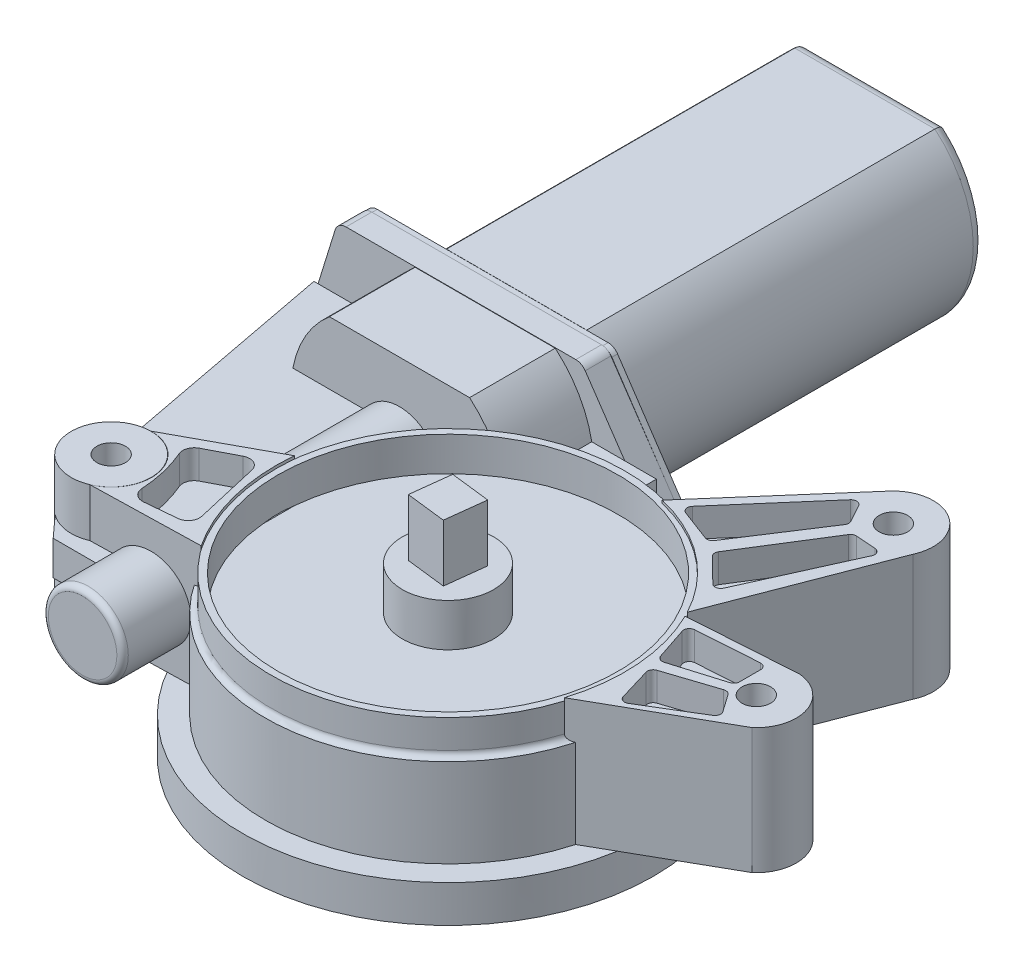
SolidWorks part; units mm, degrees
ref_plane "Спереди" through (0, 0, 0) normal (0, 0, 1) x (1, 0, 0)
ref_plane "Сверху" through (0, 0, 0) normal (0, 1, 0) x (1, 0, 0)
ref_plane "Справа" through (0, 0, 0) normal (1, 0, 0) x (0, 0, -1)
sketch "Эскиз3" plane through (0, 0, 0) normal (0, 0, 1) x (1, 0, 0)
  line L0 (0, 0) -> (56.6194, 0) construction
  line L1 (-12.278, 14.5) -> (12.278, 14.5)
  line L2 (-12.278, -14.5) -> (12.278, -14.5)
  arc A0 (-12.278, 14.5) -> (-12.278, -14.5) centre (0, 0) ccw
  arc A1 (12.278, -14.5) -> (12.278, 14.5) centre (0, 0) ccw
  dimension "D1" = 14.5
extrude "Вытянуть1" add sketch "Эскиз3" along normal blind 63
sketch "Эскиз4" plane through (0, 0, 0) normal (0, 0, -1) x (-1, 0, 0)
  circle A0 centre (0, 0) radius 6.75
extrude "Вытянуть2" add sketch "Эскиз4" along normal blind 5
sketch "Эскиз5" plane through (0, 0, -5) normal (0, 0, -1) x (-1, 0, 0)
  circle A0 centre (0, 0) radius 2.5
extrude "Вытянуть3" add sketch "Эскиз5" along normal blind 2 draft 33
sketch "Эскиз7" plane through (0, 0, 63) normal (0, 0, 1) x (1, 0, 0)
  line L0 (-29.9997, 1.118) -> (-26.3061, 13.0633)
  line L1 (-24.3954, -14.4725) -> (27.9997, -14.4725)
  line L2 (-29.9997, -1.118) -> (-29.9997, 1.118)
  line L3 (-24.3954, 14.4725) -> (16.0407, 14.4725)
  line L4 (29.9997, -12.4725) -> (29.9997, -5.3043)
  line L5 (-26.4064, -12.739) -> (20.265, 9.7763) construction
  line L6 (-26.4064, 12.739) -> (29.9997, -14.4725) construction
  line L7 (-29.9997, 0) -> (-36.554, 0) construction
  line L8 (-29.9997, -1.118) -> (-26.3061, -13.0633)
  line L9 (17.7001, 13.5889) -> (29.6591, -4.1879)
  arc A0 (-24.3954, 14.4725) -> (-26.3061, 13.0633) centre (-24.3954, 12.4725) ccw
  arc A1 (-24.3954, -14.4725) -> (-26.3061, -13.0633) centre (-24.3954, -12.4725) cw
  arc A2 (17.7001, 13.5889) -> (16.0407, 14.4725) centre (16.0407, 12.4725) ccw
  arc A3 (29.6591, -4.1879) -> (29.9997, -5.3043) centre (27.9997, -5.3043) cw
  arc A4 (27.9997, -14.4725) -> (29.9997, -12.4725) centre (27.9997, -12.4725) ccw
  point P0 (0, 0)
  point P14 (-25.8704, 14.4725)
  point P17 (-25.8704, -14.4725)
  dimension "D1" = 2
  dimension "D2" = 2
extrude "Вытянуть4" add sketch "Эскиз7" along normal blind 1
ref_plane "Плоскость1" through (0, -16.5, 0) normal (0, -1, 0) x (1, 0, 0)
sketch "Эскиз8" plane through (0, -16.5, 0) normal (0, -1, 0) x (1, 0, 0)
  line L0 (0, 0) -> (0, 81.1276) construction
  line L1 (23.2237, 64) -> (84.0137, 64) construction
  circle A0 centre (34, 109) radius 36
  dimension "D1" = 45
  dimension "D2" = 34
extrude "Вытянуть5" add sketch "Эскиз8" against normal blind 6.5 separate body
sketch "Эскиз10" plane through (0, -10, 0) normal (0, -1, 0) x (-1, 0, 0)
  circle A0 centre (-34, -109) radius 32
extrude "Вытянуть6" add sketch "Эскиз10" against normal blind 15.5
sketch "Эскиз11" plane through (0, 5.5, 0) normal (0, 1, 0) x (1, 0, 0)
  circle A0 centre (34, -109) radius 31
  circle A1 centre (34, -109) radius 29.8
extrude "Вытянуть7" add sketch "Эскиз11" along normal blind 6
fillet "Скругление1" radius 1 1 edges at (34, 5.5, 78)
sketch "Эскиз12" plane through (0, -16.5, 0) normal (0, 1, 0) x (-1, 0, 0)
  line L0 (-34, 145) -> (-34, 159.637) construction
  line L1 (-70, 109) -> (-97.217, 109) construction
  line L2 (-44.5372, 139.4635) -> (-23.4628, 139.4635)
  line L3 (-21.7278, 136.4684) -> (-32.2651, 118.0963)
  line L4 (-46.2722, 136.4684) -> (-35.7349, 118.0963)
  line L5 (-16.3477, 133.3622) -> (-26.9898, 115.0506)
  line L6 (-4.0756, 112.1062) -> (-25.2549, 112.0457)
  line L7 (-12.8865, 133.3573) -> (-2.3492, 115.1062)
  line L8 (-4.0756, 105.8938) -> (-25.2549, 105.9543)
  line L9 (-16.3477, 84.6378) -> (-26.9898, 102.9494)
  line L10 (-2.3492, 102.8938) -> (-12.8865, 84.6427)
  line L11 (-21.7278, 81.5316) -> (-32.2651, 99.9037)
  line L12 (-46.2722, 81.5316) -> (-35.7349, 99.9037)
  line L13 (-23.4628, 78.5365) -> (-44.5372, 78.5365)
  line L14 (-51.6523, 84.6378) -> (-41.0102, 102.9494)
  line L15 (-63.9244, 105.8938) -> (-42.7451, 105.9543)
  line L16 (-55.1135, 84.6427) -> (-65.6508, 102.8938)
  line L17 (-63.9244, 112.1062) -> (-42.7451, 112.0457)
  line L18 (-51.6523, 133.3622) -> (-41.0102, 115.0506)
  line L19 (-65.6508, 115.1062) -> (-55.1135, 133.3573)
  arc A0 (-23.4628, 139.4635) -> (-21.7278, 136.4684) centre (-23.4628, 137.4635) cw
  arc A1 (-46.2722, 136.4684) -> (-44.5372, 139.4635) centre (-44.5372, 137.4635) cw
  arc A2 (-32.2651, 118.0963) -> (-35.7349, 118.0963) centre (-34, 119.0914) cw
  arc A3 (-25.2549, 112.0457) -> (-26.9898, 115.0506) centre (-25.2606, 114.0457) cw
  arc A4 (-2.3492, 115.1062) -> (-4.0756, 112.1062) centre (-4.0813, 114.1062) cw
  arc A5 (-16.3477, 133.3622) -> (-12.8865, 133.3573) centre (-14.6185, 132.3573) cw
  arc A6 (-26.9898, 102.9494) -> (-25.2549, 105.9543) centre (-25.2606, 103.9543) cw
  arc A7 (-12.8865, 84.6427) -> (-16.3477, 84.6378) centre (-14.6185, 85.6427) cw
  arc A8 (-4.0756, 105.8938) -> (-2.3492, 102.8938) centre (-4.0813, 103.8938) cw
  arc A9 (-35.7349, 99.9037) -> (-32.2651, 99.9037) centre (-34, 98.9086) cw
  arc A10 (-44.5372, 78.5365) -> (-46.2722, 81.5316) centre (-44.5372, 80.5365) cw
  arc A11 (-21.7278, 81.5316) -> (-23.4628, 78.5365) centre (-23.4628, 80.5365) cw
  arc A12 (-42.7451, 105.9543) -> (-41.0102, 102.9494) centre (-42.7394, 103.9543) cw
  arc A13 (-65.6508, 102.8938) -> (-63.9244, 105.8938) centre (-63.9187, 103.8938) cw
  arc A14 (-51.6523, 84.6378) -> (-55.1135, 84.6427) centre (-53.3815, 85.6427) cw
  arc A15 (-41.0102, 115.0506) -> (-42.7451, 112.0457) centre (-42.7394, 114.0457) cw
  arc A16 (-55.1135, 133.3573) -> (-51.6523, 133.3622) centre (-53.3815, 132.3573) cw
  arc A17 (-63.9244, 112.1062) -> (-65.6508, 115.1062) centre (-63.9187, 114.1062) cw
  point P9 (-20.0101, 139.4635)
  point P12 (-47.9899, 139.4635)
  point P15 (-34, 115.0714)
  dimension "D1" = 2
extrude "Вытянуть8" cut sketch "Эскиз12" along normal blind 1.2
sketch "Эскиз13" plane through (0, 5.5, 0) normal (0, 1, 0) x (1, 0, 0)
  circle A0 centre (34, -109) radius 8
extrude "Вытянуть9" add sketch "Эскиз13" along normal blind 7.5
sketch "Эскиз14" plane through (0, 13, 0) normal (0, 1, 0) x (1, 0, 0)
  line L1 (30.9351, -105.1133) -> (30.1133, -112.0649)
  line L2 (30.1133, -112.0649) -> (37.0649, -112.8867)
  line L3 (37.0649, -112.8867) -> (37.8867, -105.9351)
  line L4 (37.8867, -105.9351) -> (30.9351, -105.1133)
  circle A0 centre (34, -109) radius 3.5 construction
extrude "Вытянуть10" add sketch "Эскиз14" along normal blind 10
sketch "Эскиз15" plane through (0, 0, 64) normal (0, 0, 1) x (1, 0, 0)
  circle A0 centre (0, 0) radius 7
extrude "Вытянуть11" add sketch "Эскиз15" along normal blind 75
sketch "Эскиз16" plane through (0, 0, 64) normal (0, 0, 1) x (1, 0, 0)
  line L0 (12.278, 14.5) -> (-12.278, 14.5)
  line L1 (12.278, 14.5) -> (-12.278, 14.5) construction
  line L2 (12.278, -14.5) -> (-12.278, -14.5)
  arc A0 (-12.278, 14.5) -> (-12.278, -14.5) centre (0, 0) ccw
  arc A1 (12.278, -14.5) -> (12.278, 14.5) centre (0, 0) ccw
extrude "Вытянуть12" add sketch "Эскиз16" along normal blind 19.5
sketch "Эскиз17" plane through (0, 0, 64) normal (0, 0, 1) x (1, 0, 0)
  line L0 (-26.2716, 13.1654) -> (-29.9899, 1.1498)
  line L1 (15.8793, 14.5741) -> (-24.361, 14.5741)
  line L2 (30.0005, -5.2705) -> (30.0005, -12.4733)
  line L3 (28.0005, -14.4733) -> (-24.3951, -14.4733)
  line L4 (-29.9899, 1.1498) -> (-29.9899, -1.1315)
  line L7 (-29.9899, -1.1315) -> (-26.3061, -13.0633)
  line L8 (-26.3061, 13.0633) -> (-29.9997, 1.118) construction
  line L9 (29.6549, -4.1467) -> (17.5338, 13.6979)
  arc A0 (-26.2716, 13.1654) -> (-24.361, 14.5741) centre (-24.361, 12.5741) cw
  arc A1 (-26.3061, -13.0633) -> (-24.3951, -14.4733) centre (-24.3951, -12.4733) ccw
  arc A2 (-24.3954, 14.4725) -> (-26.3061, 13.0633) centre (-24.3954, 12.4725) ccw construction
  arc A3 (15.8793, 14.5741) -> (17.5338, 13.6979) centre (15.8793, 12.5741) cw
  arc A4 (28.0005, -14.4733) -> (30.0005, -12.4733) centre (28.0005, -12.4733) ccw
  arc A5 (29.6549, -4.1467) -> (30.0005, -5.2705) centre (28.0005, -5.2705) cw
  dimension "D1" = 2
  dimension "D2" = 2
  dimension "D3" = 2
  dimension "D4" = 2
extrude "Вытянуть13" add sketch "Эскиз17" along normal blind 4.5
fillet "Скругление2" radius 1 1 edges at (7, 0, 139)
ref_plane "Плоскость2" through (0, -2.5, 0) normal (0, -1, 0) x (1, 0, 0)
ref_plane "Плоскость3" through (0, -10, 0) normal (0, 1, 0) x (-1, 0, 0)
sketch "Эскиз19" plane through (0, -10, 0) normal (0, 1, 0) x (-1, 0, 0)
  line L1 (-16.0407, 64) -> (24.3954, 64) construction
  line L2 (0, 0) -> (0, -45.8668) construction
  circle A0 centre (13, 121) radius 7
  circle A1 centre (13, 121) radius 2.5
  dimension "D1" = 57
  dimension "D2" = 13
extrude "Вытянуть16" add sketch "Эскиз19" along normal blind 22
sketch "Эскиз18" plane through (0, -2.5, 0) normal (0, -1, 0) x (1, 0, 0)
  line L0 (-29.9899, 68.5) -> (-20, 121)
  line L1 (-13.853, 130.3043) -> (2.1987, 130.3043)
  line L2 (-17.229, 126.5781) -> (-13.853, 130.3043)
  line L3 (30.0005, 77.2509) -> (30.0005, 68.5)
  line L4 (-29.9899, 68.5) -> (30.0005, 68.5)
  line L5 (2.1987, 112.5605) -> (2.1987, 130.3043)
  circle A0 centre (-13, 121) radius 7 construction
  arc A1 (30.0005, 77.2509) -> (2.1987, 112.5605) centre (34, 109) cw
  arc A2 (18.1865, 81.1803) -> (4.3301, 120.9874) centre (34, 109) ccw construction
  arc A4 (-20, 121) -> (-17.229, 126.5781) centre (-13, 121) ccw
extrude "Вытянуть15" add sketch "Эскиз18" against normal blind 6
sketch "Эскиз20" plane through (0, -10, 0) normal (0, 1, 0) x (-1, 0, 0)
  line L0 (13.0336, 113.982) -> (-3.2391, 105.157)
  line L1 (10.2818, 127.4507) -> (-8.7473, 126.9805)
  arc A0 (17.229, 126.5781) -> (6.0622, 121.9309) centre (13, 121) ccw construction
  circle A1 centre (13, 121) radius 7 construction
  arc A6 (-3.2391, 105.157) -> (-8.7473, 126.9805) centre (-37.2063, 108.1908) ccw
  arc A7 (13.0336, 113.982) -> (10.2818, 127.4507) centre (12.9558, 120.9816) cw
  arc A8 (-16.3719, 83.5) -> (-17.8536, 82.537) centre (-34, 109) ccw construction
extrude "Вытянуть21" add sketch "Эскиз20" along normal blind 22 separate body
sketch "Эскиз21" plane through (0, 12, 0) normal (0, 1, 0) x (1, 0, 0)
  line L0 (-6.2428, -112.3443) -> (-1.1739, -109.7169)
  line L1 (1.6954, -111.0431) -> (4.3195, -122.4246)
  line L2 (2.554, -124.8655) -> (-2.9539, -125.3725)
  arc A0 (-7.1603, -114.9089) -> (-5.1338, -123.4968) centre (-30.6107, -124.9754) cw
  arc A1 (-6.2428, -112.3443) -> (-7.1603, -114.9089) centre (-5.3224, -114.12) ccw
  arc A2 (1.6954, -111.0431) -> (-1.1739, -109.7169) centre (-0.2535, -111.4925) ccw
  arc A3 (2.554, -124.8655) -> (4.3195, -122.4246) centre (2.3706, -122.874) ccw
  arc A4 (-5.1338, -123.4968) -> (-2.9539, -125.3725) centre (-3.1372, -123.381) ccw
  dimension "D1" = 2
extrude "Вытянуть23" cut sketch "Эскиз21" against normal blind 5
sketch "Эскиз22" plane through (0, -10, 0) normal (0, -1, 0) x (1, 0, 0)
  line L0 (-2.6512, 125.3994) -> (3.0523, 125.1404)
  line L1 (4.874, 122.5572) -> (1.4559, 111.3884)
  line L2 (-1.2936, 110.1573) -> (-6.317, 112.4722)
  arc A0 (-4.728, 123.6372) -> (-7.267, 115.1865) centre (-30.0699, 126.6445) cw
  arc A1 (-2.6512, 125.3994) -> (-4.728, 123.6372) centre (-2.742, 123.4015) ccw
  arc A2 (4.874, 122.5572) -> (3.0523, 125.1404) centre (2.9616, 123.1425) ccw
  arc A3 (-1.2936, 110.1573) -> (1.4559, 111.3884) centre (-0.4566, 111.9737) ccw
  arc A4 (-7.267, 115.1865) -> (-6.317, 112.4722) centre (-5.48, 114.2886) ccw
extrude "Вытянуть24" cut sketch "Эскиз22" against normal blind 5
sketch "Эскиз23" plane through (0, -10, 0) normal (0, 1, 0) x (-1, 0, 0)
  line L0 (0, 0) -> (0, -17.6371) construction
  line L1 (-27.9997, 63) -> (-142.4972, 63) construction
  line L2 (-60.6873, 58.442) -> (-42.1989, 79.6831)
  line L3 (-72.3707, 65.9008) -> (-61.3848, 94.4717)
  arc A0 (-72.3707, 65.9008) -> (-60.6873, 58.442) centre (-66, 63) ccw
  circle A1 centre (-66, 63) radius 2.5
  circle A2 centre (-34, 109) radius 31 construction
  arc A5 (-42.1989, 79.6831) -> (-61.3848, 94.4717) centre (-35.4039, 108.3383) cw
  dimension "D1" = 66
extrude "Вытянуть27" add sketch "Эскиз23" along normal up to surface (22 mm away) separate body up to face at (-1.718, 12, 118.0081)
sketch "Эскиз24" plane through (0, 12, 0) normal (0, 1, 0) x (1, 0, 0)
  line L0 (66, -63) -> (69.7667, -57.0998) construction
  line L1 (45.7799, -77.9636) -> (58.6063, -63.1419)
  line L2 (60.2372, -63.3116) -> (61.9309, -66.3685)
  line L3 (61.8946, -67.3981) -> (52.8928, -81.2471)
  line L4 (51.701, -81.6376) -> (46.1827, -79.5534)
  line L5 (55.112, -83.8152) -> (59.3252, -87.9437)
  line L6 (63.7383, -68.5752) -> (54.9646, -82.5698)
  line L7 (68.1428, -68.3587) -> (64.6571, -68.1089)
  line L8 (60.9369, -87.6399) -> (68.9832, -69.7666)
  arc A1 (60.2372, -63.3116) -> (58.6063, -63.1419) centre (59.3625, -63.7963) ccw
  arc A2 (61.8946, -67.3981) -> (61.9309, -66.3685) centre (61.0562, -66.8531) ccw
  arc A3 (51.701, -81.6376) -> (52.8928, -81.2471) centre (52.0543, -80.7021) ccw
  arc A4 (45.7799, -77.9636) -> (46.1827, -79.5534) centre (46.5361, -78.6179) ccw
  arc A5 (60.9369, -87.6399) -> (59.3252, -87.9437) centre (60.0251, -87.2294) cw
  arc A6 (55.112, -83.8152) -> (54.9646, -82.5698) centre (55.8119, -83.1009) cw
  arc A7 (63.7383, -68.5752) -> (64.6571, -68.1089) centre (64.5856, -69.1064) cw
  arc A8 (68.1428, -68.3587) -> (68.9832, -69.7666) centre (68.0714, -69.3561) cw
  dimension "D1" = 1
extrude "Вытянуть28" cut sketch "Эскиз24" against normal blind 5
sketch "Эскиз25" plane through (0, -10, 0) normal (0, -1, 0) x (1, 0, 0)
  line L0 (46.1827, 79.5534) -> (51.701, 81.6376)
  line L1 (52.8928, 81.2471) -> (61.8946, 67.3981)
  line L2 (61.9309, 66.3685) -> (60.2372, 63.3116)
  line L3 (58.6063, 63.1419) -> (45.7799, 77.9636)
  line L4 (66, 63) -> (69.7667, 57.0998) construction
  line L5 (59.3252, 87.9437) -> (55.112, 83.8152)
  line L6 (54.9646, 82.5698) -> (63.7383, 68.5752)
  line L7 (64.6571, 68.1089) -> (68.1428, 68.3587)
  line L8 (68.9832, 69.7666) -> (60.9369, 87.6399)
  arc A0 (55.112, 83.8152) -> (54.9646, 82.5698) centre (55.8119, 83.1009) ccw
  arc A1 (60.2372, 63.3116) -> (58.6063, 63.1419) centre (59.3625, 63.7963) cw
  arc A2 (61.9309, 66.3685) -> (61.8946, 67.3981) centre (61.0562, 66.8531) ccw
  arc A3 (51.701, 81.6376) -> (52.8928, 81.2471) centre (52.0543, 80.7021) cw
  arc A4 (45.7799, 77.9636) -> (46.1827, 79.5534) centre (46.5361, 78.6179) cw
  arc A5 (64.6571, 68.1089) -> (63.7383, 68.5752) centre (64.5856, 69.1064) cw
  arc A6 (68.1428, 68.3587) -> (68.9832, 69.7666) centre (68.0714, 69.3561) ccw
  arc A7 (60.9369, 87.6399) -> (59.3252, 87.9437) centre (60.0251, 87.2294) ccw
  dimension "D1" = 1
extrude "Вытянуть29" cut sketch "Эскиз25" against normal blind 5
sketch "Эскиз26" plane through (0, -10, 0) normal (0, 1, 0) x (-1, 0, 0)
  line L0 (-27.2099, 64) -> (-121.7072, 64) construction
  line L1 (0, 0) -> (0, 18.5901) construction
  line L2 (-80.6673, 94.0319) -> (-61.7986, 95.2801)
  line L3 (-84.5472, 106.3219) -> (-63.6005, 118.2094)
  arc A0 (-84.5472, 106.3219) -> (-80.6673, 94.0319) centre (-80, 101) ccw
  circle A1 centre (-80, 101) radius 2.5
  circle A2 centre (-34, 109) radius 31 construction
  arc A3 (-61.7986, 95.2801) -> (-63.6005, 118.2094) centre (-34, 109) cw
  dimension "D1" = 37
  dimension "D2" = 80
extrude "Вытянуть30" add sketch "Эскиз26" along normal up to surface (22 mm away) up to face at (62.0028, 12, 77.1097)
sketch "Эскиз27" plane through (0, 12, 0) normal (0, 1, 0) x (1, 0, 0)
  line L0 (80, -101) -> (86.6753, -98.8926) construction
  line L1 (63.8177, -97.8045) -> (65.7058, -103.4687)
  line L2 (66.9436, -104.1098) -> (75.8239, -101.4281)
  line L3 (76.5348, -100.4708) -> (76.5348, -96.7619)
  line L4 (75.4675, -95.7641) -> (64.6991, -96.4906)
  line L5 (67.5247, -105.9505) -> (76.3351, -103.0473)
  line L6 (77.4668, -103.4229) -> (79.5963, -106.4595)
  line L7 (79.2954, -107.8892) -> (70.0618, -113.4773)
  line L8 (68.5858, -112.9076) -> (66.8794, -107.1861)
  arc A1 (76.5348, -96.7619) -> (75.4675, -95.7641) centre (75.5348, -96.7619) ccw
  arc A2 (75.8239, -101.4281) -> (76.5348, -100.4708) centre (75.5348, -100.4708) ccw
  arc A3 (65.7058, -103.4687) -> (66.9436, -104.1098) centre (66.6545, -103.1525) ccw
  arc A4 (64.6991, -96.4906) -> (63.8177, -97.8045) centre (64.7664, -97.4883) ccw
  arc A5 (76.3351, -103.0473) -> (77.4668, -103.4229) centre (76.6481, -103.9971) cw
  arc A6 (79.5963, -106.4595) -> (79.2954, -107.8892) centre (78.7776, -107.0337) cw
  arc A7 (70.0618, -113.4773) -> (68.5858, -112.9076) centre (69.544, -112.6218) cw
  arc A8 (66.8794, -107.1861) -> (67.5247, -105.9505) centre (67.8377, -106.9003) cw
  dimension "D1" = 1
sketch "Эскиз28" plane through (0, -10, 0) normal (0, -1, 0) x (1, 0, 0)
  line L0 (80, 101) -> (86.5648, 98.9275) construction
  line L2 (65.7058, 103.4687) -> (63.8177, 97.8045)
  line L3 (64.6991, 96.4906) -> (75.4675, 95.7641)
  line L4 (76.5348, 96.7619) -> (76.5348, 100.4708)
  line L5 (75.8239, 101.4281) -> (66.9436, 104.1098)
  line L6 (70.0618, 113.4773) -> (79.2954, 107.8892)
  line L7 (79.5963, 106.4595) -> (77.4668, 103.4229)
  line L8 (76.3351, 103.0473) -> (67.5247, 105.9505)
  line L9 (66.8794, 107.1861) -> (68.5858, 112.9076)
  arc A0 (66.9436, 104.1098) -> (65.7058, 103.4687) centre (66.6545, 103.1525) ccw
  arc A1 (76.5348, 100.4708) -> (75.8239, 101.4281) centre (75.5348, 100.4708) ccw
  arc A2 (75.4675, 95.7641) -> (76.5348, 96.7619) centre (75.5348, 96.7619) ccw
  arc A3 (63.8177, 97.8045) -> (64.6991, 96.4906) centre (64.7664, 97.4883) ccw
  arc A4 (68.5858, 112.9076) -> (70.0618, 113.4773) centre (69.544, 112.6218) cw
  arc A5 (79.2954, 107.8892) -> (79.5963, 106.4595) centre (78.7776, 107.0337) cw
  arc A6 (77.4668, 103.4229) -> (76.3351, 103.0473) centre (76.6481, 103.9971) cw
  arc A7 (67.5247, 105.9505) -> (66.8794, 107.1861) centre (67.8377, 106.9003) cw
  dimension "D1" = 1
extrude "Вытянуть31" cut sketch "Эскиз27" against normal blind 5
extrude "Вытянуть32" cut sketch "Эскиз28" against normal blind 5
fillet "Скругление3" radius 2 4 edges at (0, -14.5, 0) (19, 0, 0) (-19, 0, 0) (0, 14.5, 0)
fillet "Скругление4" radius 1 1 edges at (-6.75, 0, -5)
fillet "Скругление5" radius 0.5 1 edges at (-1.2012, 0, -7)
